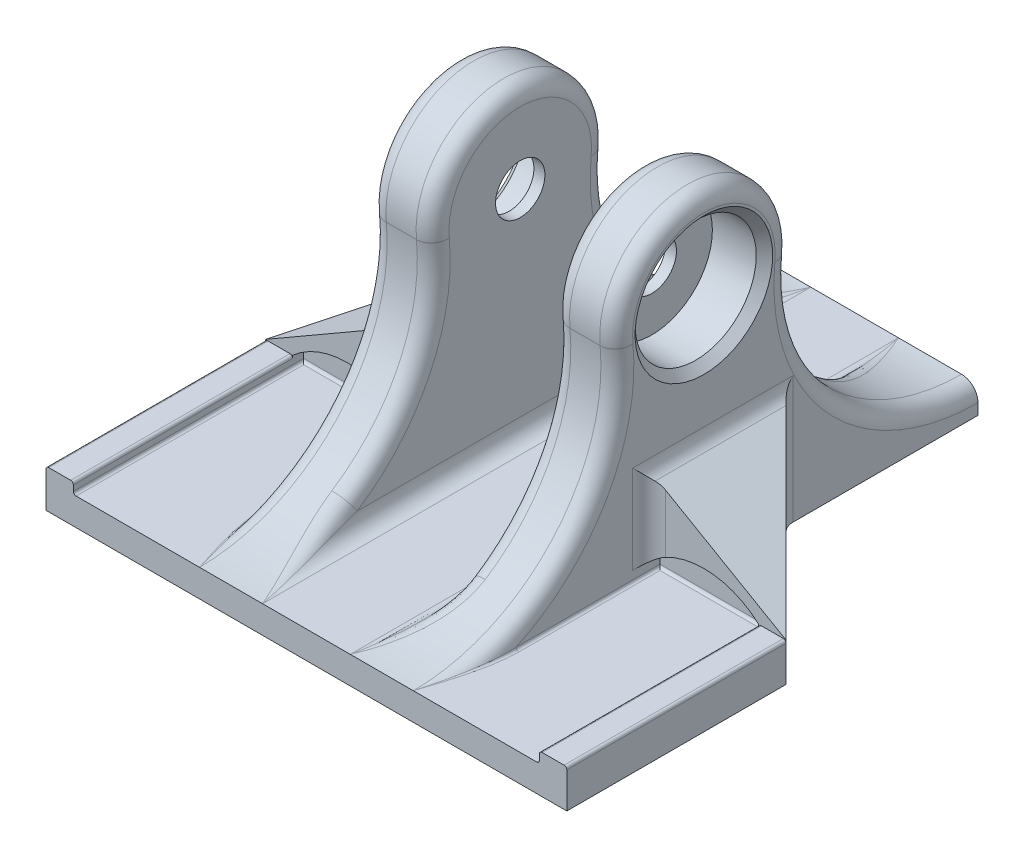
SolidWorks part; units mm, degrees
ref_plane "Front Plane" through (0, 0, 0) normal (0, 0, 1) x (1, 0, 0)
ref_plane "Top Plane" through (0, 0, 0) normal (0, 1, 0) x (1, 0, 0)
ref_plane "Right Plane" through (0, 0, 0) normal (1, 0, 0) x (0, 0, -1)
sketch "Sketch1" plane through (0, 0, 0) normal (1, 0, 0) x (0, 0, -1)
  line L0 (-50, 0) -> (50, 0)
  line L1 (-50, 0) -> (-50, 5)
  line L2 (0, 0) -> (0, 60) construction
  line L3 (50, 0) -> (50, 5)
  arc A0 (-50, 5) -> (-15.9276, 42.4796) centre (-50, 39.2273) ccw
  arc A1 (-15.9276, 42.4796) -> (15.9276, 42.4796) centre (0, 44) cw
  arc A3 (50, 5) -> (15.9276, 42.4796) centre (50, 39.2273) cw
  circle A4 centre (0, 44) radius 4.5
  point P13 (0, 60)
  dimension "D4" = 9
  dimension "D5" = 16
  dimension "D1" = 50
  dimension "D2" = 5
  dimension "D3" = 60
extrude "Boss-Extrude1" add sketch "Sketch1" along normal mid plane 45 contours L0 L2 A1 A0 L1 | L2 L0 L3 A3 A1 region at (0, 21.5411, 0)
ref_plane "Plane1" through (0, 5, 0) normal (0, -1, 0) x (-1, 0, 0)
sketch "Sketch2" plane through (0, 5, 0) normal (0, -1, 0) x (-1, 0, 0)
  line L0 (-22.5, -50) -> (22.5, -50) construction
  line L1 (-11, 50) -> (11, 50)
  line L2 (-11, 50) -> (-11, -50)
  line L3 (-11, -50) -> (11, -50)
  line L4 (11, 50) -> (11, -50)
  line L5 (-11, 50) -> (11, -50) construction
  line L6 (-11, -50) -> (11, 50) construction
  point P0 (0, 0)
  dimension "D1" = 22
extrude "Cut-Extrude1" cut sketch "Sketch2" against normal through all contours L2 L3 L4 L1
sketch "Sketch8" plane through (0, 5, 0) normal (0, 1, 0) x (1, 0, 0)
  line L0 (-22.5, -50) -> (-47.5, -50)
  line L1 (-47.5, -50) -> (-47.5, -10)
  line L2 (-47.5, -10) -> (-22.5, 15)
  line L3 (-22.5, 50) -> (-22.5, 15.7727) construction
  line L4 (-22.5, 15) -> (-22.5, -50)
  dimension "D1" = 25
  dimension "D2" = 40
  dimension "D3" = 45
extrude "Boss-Extrude2" add sketch "Sketch8" against normal up to surface (5 mm away) up to face at (0, 0, 0)
sketch "Sketch9" plane through (0, 5, 0) normal (0, 1, 0) x (1, 0, 0)
  line L0 (-22.5, -50) -> (-22.5, 15) construction
  line L1 (-47.5, -50) -> (-42.5, -50)
  line L2 (-47.5, -50) -> (-47.5, -10)
  line L3 (-47.5, -10) -> (-42.5, -10)
  line L4 (-42.5, -50) -> (-42.5, -10)
  point P7 (0, 0)
  dimension "D1" = 20
extrude "Boss-Extrude3" add sketch "Sketch9" along normal blind 2
sketch "Sketch10" plane through (0, 0, 10) normal (0, 0, -1) x (-1, 0, 0)
  line L0 (47.5, 7) -> (22.5, 21.4338)
  line L1 (22.5, 21.4338) -> (22.5, 5)
  line L2 (22.5, 5) -> (47.5, 5)
  line L3 (47.5, 5) -> (47.5, 7)
  line L4 (22.5, 5) -> (22.5, 42.4796) construction
  line L5 (-52.25, 5) -> (52.25, 5) construction
  point P5 (0, 0)
  dimension "D1" = 30
extrude "Boss-Extrude4" add sketch "Sketch10" along normal up to surface (25 mm away) up to face at (-35, 2.5, -2.5)
sketch "Sketch11" plane through (0, 0, 10) normal (0, 0, 1) x (1, 0, 0)
  line L0 (-42.5, 7) -> (-42.5, 5)
  line L1 (-42.5, 5) -> (-22.5, 5)
  line L2 (-22.5, 5) -> (-22.5, 7)
  line L3 (-22.5, 21.4338) -> (-22.5, 5) construction
  arc A0 (-22.5, 7) -> (-42.5, 7) centre (-32.5, -4.1803) ccw
  point P10 (0, 0)
  point P11 (-32.5, 7)
  point P12 (0, 0)
  point P13 (0, 0)
  dimension "D1" = 15
extrude "Cut-Extrude5" cut sketch "Sketch11" against normal blind 2
mirror "Mirror3" about plane through (0, 0, 0) normal (1, 0, 0) of "Boss-Extrude2", "Boss-Extrude3", "Boss-Extrude4", "Cut-Extrude5"
fillet "Fillet1" radius 3 2 edges at (11, 5, 0) (-11, 5, 0)
fillet "Fillet2" radius 3 16 edges at (-22.5, 16.2035, 24.6739) (-22.5, 16.2035, -24.6739) (-10.26, 6.0271, 41.6781) (-11, 22.0155, 20.4152) (-10.26, 6.0271, -41.6781) (-11, 22.0155, -20.4152) (10.26, 6.0271, 41.6781) (11, 22.0155, 20.4152) (10.26, 6.0271, -41.6781) (11, 22.0155, -20.4152) (22.5, 16.2035, 24.6739) (-22.5, 60, 0) (-11, 60, 0) (11, 60, 0) (22.5, 16.2035, -24.6739) (22.5, 60, 0)
fillet "Fillet3" radius 0.5 12 edges at (-32.5, 5, 8) (-22.5, 5, 21.6794) (-47.5, 7, 30) (-42.5, 7, 30) (-42.5, 5, 29) (-21.8001, 5, 41.3588) (21.8001, 5, 41.3588) (47.5, 7, 30) (42.5, 7, 30) (42.5, 5, 29) (32.5, 5, 8) (22.5, 5, 21.6794)
fillet "Fillet16" radius 3 6 edges at (-22.5, 14.2169, 10) (-22.5, 21.4338, -2.5) (-22.5, 10.7169, -15) (22.5, 10.7169, -15) (22.5, 21.4338, -2.5) (22.5, 14.2169, 10)
sketch "Sketch12" plane through (-22.5, 0, 0) normal (-1, 0, 0) x (0, 0, 1)
  circle A1 centre (0, 44) radius 11.05
  dimension "D1" = 22.1
extrude "Cut-Extrude6" cut sketch "Sketch12" against normal offset from surface (9.5 mm away) 13 up to plane "Right Plane"
mirror "Mirror4" about plane through (0, 0, 0) normal (1, 0, 0) of "Cut-Extrude6"
chamfer "Chamfer1" distance 1.5 angle 45 2 edges at (22.5, 44, 11.05) (-22.5, 44, 11.05)
